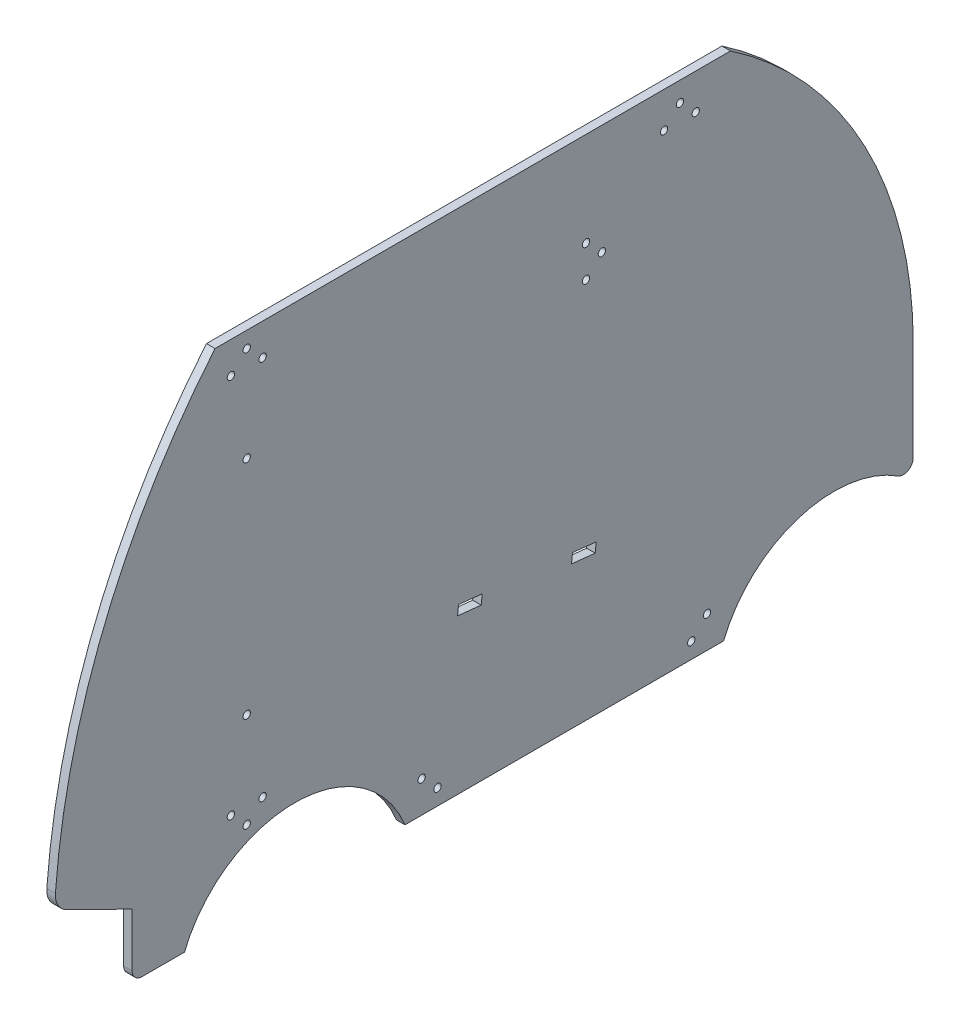
SolidWorks part; units mm, degrees
material "Acrylic (Medium-high impact)"
ref_plane "Front" through (0, 0, 0) normal (0, 0, 1) x (1, 0, 0)
ref_plane "Top" through (0, 0, 0) normal (0, 1, 0) x (1, 0, 0)
ref_plane "Right" through (0, 0, 0) normal (1, 0, 0) x (0, 0, -1)
ref_axis "side-side" through (80.9, 0, 0) along (-1, 0, 0)
ref_axis "up-down" through (0, 50, 0) along (0, -1, 0)
ref_axis "front-back" through (0, 0, -80.9) along (0, 0, 1)
sketch "Sketch1" plane through (0, 0, 0) normal (1, 0, 0) x (0, 0, -1)
  line L6 (136.2407, 32.2723) -> (136.2407, 82.1541)
  line L7 (44.044, 256) -> (-215.956, 256)
  line L8 (-290.8632, 48.3173) -> (-257.7593, 32)
  line L9 (-257.7593, 32) -> (-257.7593, 5)
  line L10 (-252.7593, 0) -> (-231.3807, 0)
  line L11 (-120.1378, 0) -> (40.6193, 0)
  line L12 (136.2407, 32.2723) -> (136.2407, 82.1541)
  line L13 (44.044, 256) -> (-215.956, 256)
  line L14 (-290.8632, 48.3173) -> (-257.7593, 32)
  line L15 (-257.7593, 32) -> (-257.7593, 5)
  line L16 (-252.7593, 0) -> (-231.3807, 0)
  line L17 (-120.1378, 0) -> (40.6193, 0)
  line L102 (-93.1211, 82.722) -> (-81.1868, 81.4676)
  line L103 (-93.1211, 82.722) -> (-93.6147, 78.0255)
  line L104 (-81.1868, 81.4676) -> (-81.6804, 76.7711)
  line L105 (-93.6147, 78.0255) -> (-81.6804, 76.7711)
  line L106 (-35.6391, 76.6803) -> (-23.7048, 75.426)
  line L107 (-35.6391, 76.6803) -> (-36.1327, 71.9839)
  line L108 (-23.7048, 75.426) -> (-24.1984, 70.7295)
  line L109 (-36.1327, 71.9839) -> (-24.1984, 70.7295)
  circle A1 centre (-286.3713, 57.4304) radius 2.3813
  circle A2 centre (-286.3713, 57.4304) radius 2.3813 construction
  arc A9 (136.2407, 82.1541) -> (44.044, 256) centre (-73.7593, 82.1541) ccw
  arc A10 (-215.956, 256) -> (-296.5014, 58.2087) centre (52.47, 31.3948) ccw
  arc A11 (-296.5014, 58.2087) -> (-290.8632, 48.3173) centre (-286.3713, 57.4304) ccw
  arc A12 (-257.7593, 5) -> (-252.7593, 0) centre (-252.7593, 5) ccw
  arc A13 (-120.1378, 0) -> (-231.3807, 0) centre (-175.7593, -22.5) ccw
  arc A14 (128.5484, 28.059) -> (40.6193, 0) centre (96.2407, -22.5) ccw
  arc A15 (128.5484, 28.059) -> (136.2407, 32.2723) centre (131.2407, 32.2723) ccw
  arc A16 (136.2407, 82.1541) -> (44.044, 256) centre (-73.7593, 82.1541) ccw
  arc A17 (-215.956, 256) -> (-296.5014, 58.2087) centre (52.47, 31.3948) ccw
  arc A18 (-296.5014, 58.2087) -> (-290.8632, 48.3173) centre (-286.3713, 57.4304) ccw
  arc A19 (-257.7593, 5) -> (-252.7593, 0) centre (-252.7593, 5) ccw
  arc A20 (-120.1378, 0) -> (-231.3807, 0) centre (-175.7593, -22.5) ccw
  arc A21 (128.5484, 28.059) -> (40.6193, 0) centre (96.2407, -22.5) ccw
  arc A22 (128.5484, 28.059) -> (136.2407, 32.2723) centre (131.2407, 32.2723) ccw
  circle A136 centre (-207.956, 48) radius 1.85 construction
  circle A137 centre (-191.956, 48) radius 1.85 construction
  circle A138 centre (-199.956, 40) radius 1.85 construction
  circle A139 centre (-199.956, 200) radius 1.85 construction
  circle A140 centre (-191.956, 240) radius 1.85 construction
  circle A141 centre (-207.956, 240) radius 1.85 construction
  circle A142 centre (-199.956, 248) radius 1.85 construction
  circle A143 centre (-207.956, 48) radius 1.85
  circle A144 centre (-191.956, 48) radius 1.85
  circle A145 centre (-199.956, 40) radius 1.85
  circle A146 centre (-199.956, 200) radius 1.85
  circle A147 centre (-191.956, 240) radius 1.85
  circle A148 centre (-207.956, 240) radius 1.85
  circle A149 centre (-199.956, 248) radius 1.85
  circle A150 centre (-199.956, 88) radius 1.85 construction
  circle A151 centre (-199.956, 88) radius 1.85
  circle A152 centre (-111.7593, 16) radius 1.85 construction
  circle A153 centre (-111.7593, 16) radius 1.85
  circle A154 centre (32.2407, 16) radius 1.85 construction
  circle A155 centre (32.2407, 16) radius 1.85
  circle A156 centre (24.2407, 8) radius 1.85 construction
  circle A157 centre (24.2407, 8) radius 1.85
  circle A158 centre (-103.7593, 8) radius 1.85 construction
  circle A159 centre (-103.7593, 8) radius 1.85
  circle A160 centre (-28.8202, 192.5) radius 1.85 construction
  circle A161 centre (-20.8202, 200.5) radius 1.85 construction
  circle A162 centre (-28.8202, 208.5) radius 1.85 construction
  circle A163 centre (26.544, 238) radius 1.85 construction
  circle A164 centre (10.544, 238) radius 1.85 construction
  circle A165 centre (18.544, 246) radius 1.85 construction
  circle A166 centre (-28.8202, 192.5) radius 1.85
  circle A167 centre (-20.8202, 200.5) radius 1.85
  circle A168 centre (-28.8202, 208.5) radius 1.85
  circle A169 centre (26.544, 238) radius 1.85
  circle A170 centre (10.544, 238) radius 1.85
  circle A171 centre (18.544, 246) radius 1.85
  dimension "D1" = 0
  dimension "D2" = 0
extrude "Boss-Extrude1" add sketch "Sketch1" along normal blind 4.318
